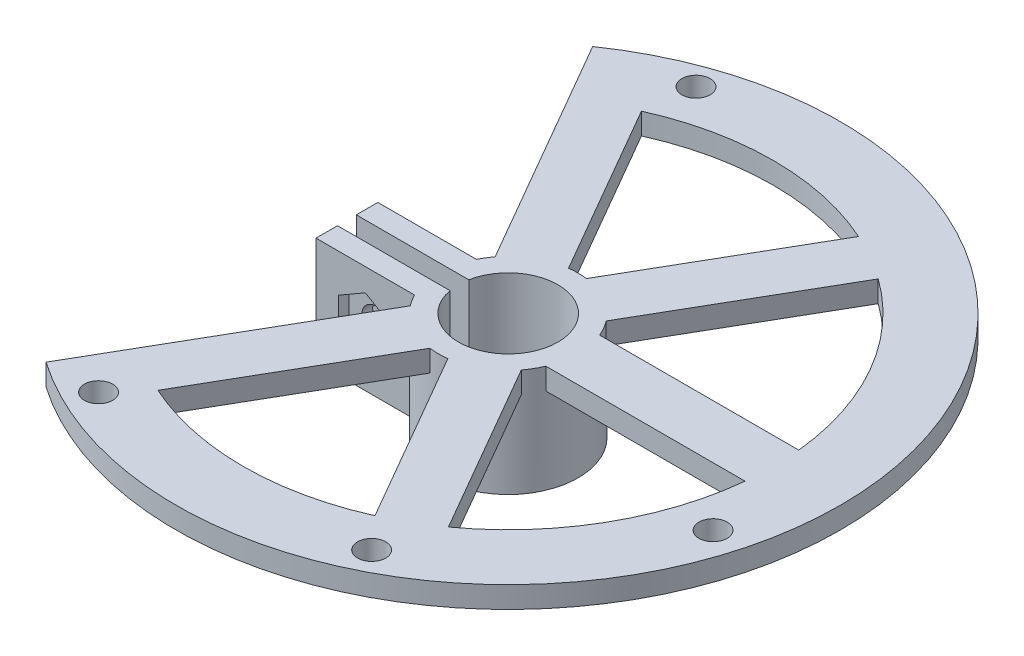
SolidWorks part; units mm, degrees
ref_plane "Front Plane" through (0, 0, 0) normal (0, 0, 1) x (1, 0, 0)
ref_plane "Top Plane" through (0, 0, 0) normal (0, 1, 0) x (1, 0, 0)
ref_plane "Right Plane" through (0, 0, 0) normal (1, 0, 0) x (0, 0, -1)
sketch "Sketch1" plane through (0, 0, 0) normal (0, 1, 0) x (1, 0, 0)
  line L0 (0, 0) -> (21.59, -6.35) construction
  line L1 (0, 0) -> (-7.62, 0) construction
  line L2 (0, 0) -> (0, 21.59) construction
  line L3 (0, 21.59) -> (-7.62, 21.59) construction
  line L4 (-7.62, 0) -> (-7.62, 21.59) construction
  line L5 (0, 0) -> (21.59, 0) construction
  line L6 (0, 0) -> (0, -6.35) construction
  line L7 (0, -6.35) -> (21.59, -6.35) construction
  line L8 (21.59, 0) -> (21.59, -6.35) construction
  line L9 (0, 0) -> (-10.16, 0) construction
  line L10 (0, 0) -> (0, -20.32) construction
  line L11 (0, -20.32) -> (-10.16, -20.32) construction
  line L12 (-10.16, 0) -> (-10.16, -20.32) construction
  line L13 (0, 0) -> (10.16, 0) construction
  line L14 (0, 0) -> (0, -20.32) construction
  line L15 (0, -20.32) -> (10.16, -20.32) construction
  line L16 (10.16, 0) -> (10.16, -20.32) construction
  line L17 (23.6985, -2.54) -> (28.16, -2.54)
  line L18 (-13.208, -20.701) -> (0, 0) construction
  line L19 (0, 0) -> (19.812, 0) construction
  line L20 (0, 0) -> (0, -10.668) construction
  line L21 (0, -10.668) -> (19.812, -10.668) construction
  line L22 (19.812, 0) -> (19.812, -10.668) construction
  line L23 (0, 0) -> (6.223, 0) construction
  line L24 (0, 0) -> (0, -21.844) construction
  line L25 (0, -21.844) -> (6.223, -21.844) construction
  line L26 (6.223, 0) -> (6.223, -21.844) construction
  line L27 (0, 0) -> (12.065, 0) construction
  line L28 (0, 0) -> (0, 19.431) construction
  line L29 (0, 19.431) -> (12.065, 19.431) construction
  line L30 (12.065, 0) -> (12.065, 19.431) construction
  line L31 (0, 0) -> (-13.208, 0) construction
  line L32 (0, 0) -> (0, -26.289) construction
  line L33 (0, -26.289) -> (-13.208, -26.289) construction
  line L34 (-13.208, 0) -> (-13.208, -26.289) construction
  line L35 (0, 0) -> (-7.62, 0) construction
  line L36 (0, 0) -> (0, -26.289) construction
  line L37 (0, -26.289) -> (-7.62, -26.289) construction
  line L38 (-7.62, 0) -> (-7.62, -26.289) construction
  line L39 (0, 0) -> (-13.208, 0) construction
  line L40 (0, 0) -> (0, -20.701) construction
  line L41 (0, -20.701) -> (-13.208, -20.701) construction
  line L42 (-13.208, 0) -> (-13.208, -20.701) construction
  line L44 (-8.62, -26.289) -> (-12.208, -26.289)
  line L45 (-13.208, -25.289) -> (-13.208, -20.9928)
  line L47 (-13.051, -20.455) -> (-11.5519, -18.1054)
  line L48 (-7.62, -25.289) -> (-7.62, -19.6963)
  line L49 (0, 0) -> (29.16, 0) construction
  line L50 (0, 0) -> (0, -6.35) construction
  line L51 (0, -6.35) -> (29.16, -6.35) construction
  line L52 (29.16, 0) -> (29.16, -6.35) construction
  line L53 (0, 0) -> (23.368, 0) construction
  line L54 (0, 0) -> (0, -2.54) construction
  line L55 (0, -2.54) -> (23.368, -2.54) construction
  line L56 (23.368, 0) -> (23.368, -2.54) construction
  line L57 (21.59, -8.35) -> (28.16, -8.35)
  line L58 (29.16, -7.35) -> (29.16, -3.54)
  line L59 (23.1026, -2.737) -> (20.3981, -4.7439)
  circle A0 centre (-7.62, 21.59) radius 1.05
  circle A1 centre (-10.16, -20.32) radius 1.05
  circle A2 centre (10.16, -20.32) radius 1.05
  circle A3 centre (21.59, -6.35) radius 1.05
  circle A4 centre (0, 0) radius 20 construction
  arc A5 (20.3981, -4.7439) -> (21.59, -8.35) centre (21.59, -6.35) ccw
  arc A10 (10.16, -20.32) -> (8.1222, -21.2169) centre (0, 0) cw construction
  arc A11 (8.8372, -23.0848) -> (11.0544, -22.1089) centre (0, 0) ccw
  arc A12 (7.4071, -19.3491) -> (9.2656, -18.5311) centre (0, 0) ccw
  arc A13 (7.4071, -19.3491) -> (8.8372, -23.0848) centre (8.1222, -21.2169) ccw
  arc A14 (11.0544, -22.1089) -> (9.2656, -18.5311) centre (10.16, -20.32) ccw
  arc A15 (-7.62, 21.59) -> (10.2434, 20.4759) centre (0, 0) cw construction
  arc A16 (11.183, 22.354) -> (-8.3189, 23.5703) centre (0, 0) ccw
  arc A17 (9.3039, 18.5979) -> (-6.9211, 19.6097) centre (0, 0) ccw
  arc A18 (9.3039, 18.5979) -> (11.183, 22.354) centre (10.2434, 20.4759) ccw
  arc A19 (-8.3189, 23.5703) -> (-6.9211, 19.6097) centre (-7.62, 21.59) ccw
  arc A21 (-10.2108, -17.7761) -> (-8.2191, -18.7802) centre (0, 0) ccw
  arc A22 (-7.62, -25.289) -> (-8.62, -26.289) centre (-8.62, -25.289) cw
  arc A23 (-12.208, -26.289) -> (-13.208, -25.289) centre (-12.208, -25.289) cw
  arc A24 (-13.208, -20.9928) -> (-13.051, -20.455) centre (-12.208, -20.9928) cw
  arc A25 (-8.2191, -18.7802) -> (-7.62, -19.6963) centre (-8.62, -19.6963) cw
  arc A26 (-11.5519, -18.1054) -> (-10.2108, -17.7761) centre (-10.7089, -18.6432) cw
  arc A27 (23.59, -6.35) -> (21.59, -4.35) centre (21.59, -6.35) ccw construction
  arc A28 (21.59, -8.35) -> (23.59, -6.35) centre (21.59, -6.35) ccw construction
  arc A29 (21.59, -4.35) -> (20.3981, -4.7439) centre (21.59, -6.35) ccw construction
  arc A30 (28.16, -8.35) -> (29.16, -7.35) centre (28.16, -7.35) ccw
  arc A31 (28.16, -2.54) -> (29.16, -3.54) centre (28.16, -3.54) cw
  arc A32 (23.6985, -2.54) -> (23.1026, -2.737) centre (23.6985, -3.54) ccw
  point P34 (9.1521, -20.7934)
  point P44 (1.4251, 22.8509)
  point P57 (-10.7576, -16.8604)
  point P59 (-7.62, -18.4915)
  point P73 (-7.62, -19.0312)
  point P76 (-11.0265, -17.282)
  point P84 (29.16, -2.54)
  dimension "D1" = 7.62
  dimension "D8" = 2.1
  dimension "D9" = 40
  dimension "D13" = 29.16
  dimension "D15" = 2
  dimension "D18" = 2.1
  dimension "D23" = 0.5
  dimension "D24" = 1
  dimension "D27" = 4
  dimension "D28" = 1
  dimension "D2" = 21.59
  dimension "D3" = 10.16
  dimension "D4" = 20.32
  dimension "D5" = 10.16
  dimension "D6" = 6.35
  dimension "D7" = 21.59
  dimension "D10" = 6.223
  dimension "D11" = 19.812
  dimension "D12" = 10.668
  dimension "D14" = 21.844
  dimension "D16" = 12.065
  dimension "D17" = 19.431
  dimension "D19" = 13.208
  dimension "D20" = 26.289
  dimension "D21" = 7.62
  dimension "D22" = 20.701
  dimension "D25" = 2.54
  dimension "D26" = 23.368
extrude "Boss-Extrude1" [suppressed] add sketch "Sketch1" along normal blind 2
sketch "Sketch2" plane through (0, 0, 0) normal (0, 1, 0) x (1, 0, 0)
  line L0 (-3.7, 0) -> (-12, 0) construction
  line L1 (-4.979, 1.5) -> (-12, 1.5) construction
  line L2 (-4.979, -1.5) -> (-12, -1.5) construction
  line L3 (-4.6637, 2.3) -> (-12, 2.3)
  line L4 (-3.6332, -0.7) -> (-12, -0.7)
  line L5 (-3.6332, 0.7) -> (-12, 0.7)
  line L6 (-4.6637, -2.3) -> (-12, -2.3)
  line L7 (-12, 2.3) -> (-12, 0.7)
  line L8 (-12, -0.7) -> (-12, -2.3)
  line L9 (0, 2.3) -> (-2.8983, 2.3) construction
  line L10 (0, 2.3) -> (-12, 2.3) construction
  line L11 (0, 1.5) -> (-3.3823, 1.5) construction
  line L12 (0, 1.5) -> (-12, 1.5) construction
  line L13 (0, 0.7) -> (-3.6332, 0.7) construction
  line L14 (0, 0.7) -> (-12, 0.7) construction
  line L15 (0, 0) -> (-3.7, 0) construction
  line L16 (0, 0) -> (-12, 0) construction
  line L17 (0, -0.7) -> (-3.6332, -0.7) construction
  line L18 (0, -0.7) -> (-12, -0.7) construction
  line L19 (0, -1.5) -> (-3.3823, -1.5) construction
  line L20 (0, -1.5) -> (-12, -1.5) construction
  line L21 (0, -2.3) -> (-2.8983, -2.3) construction
  line L22 (0, -2.3) -> (-12, -2.3) construction
  line L23 (-2.8983, 2.3) -> (-4.6637, 2.3) construction
  line L24 (-3.3823, 1.5) -> (-4.979, 1.5) construction
  line L25 (-2.8983, -2.3) -> (-4.6637, -2.3) construction
  line L26 (-3.3823, -1.5) -> (-4.979, -1.5) construction
  arc A0 (-3.6332, -0.7) -> (-3.6332, 0.7) centre (0, 0) ccw
  arc A1 (-4.6637, -2.3) -> (-4.6637, 2.3) centre (0, 0) ccw
  arc A2 (-4.979, -1.5) -> (-4.6637, -2.3) centre (0, 0) ccw construction
  arc A3 (-5.1527, -0.7) -> (-4.979, -1.5) centre (0, 0) ccw construction
  arc A4 (-4.6637, 2.3) -> (-4.979, 1.5) centre (0, 0) ccw construction
  arc A5 (-5.2, 0) -> (-5.1527, -0.7) centre (0, 0) ccw construction
  arc A6 (-4.979, 1.5) -> (-5.1527, 0.7) centre (0, 0) ccw construction
  arc A7 (-5.1527, 0.7) -> (-5.2, 0) centre (0, 0) ccw construction
  arc A8 (-3.6332, 0.7) -> (-3.7, 0) centre (0, 0) ccw construction
  arc A9 (-3.7, 0) -> (-3.6332, -0.7) centre (0, 0) ccw construction
  dimension "D1" = 7.4
  dimension "D2" = 1.5
  dimension "D3" = 12
  dimension "D4" = 1.5
  dimension "D5" = 1.5
  dimension "D6" = 0.8
  dimension "D7" = 0.8
extrude "Boss-Extrude2" add sketch "Sketch2" along normal blind 8 from offset 10 separate body
sketch "Sketch3" [suppressed] plane through (0, 2, 0) normal (0, 1, 0) x (1, 0, 0)
  line L0 (-7.62, -22.82) -> (-13.208, -22.82)
  line L1 (8.8372, -23.0848) -> (7.4071, -19.3491)
  line L2 (-7.62, -22.82) -> (-7.62, -19.6963) construction
  line L3 (-13.208, -20.9928) -> (-13.208, -22.82) construction
  line L4 (-7.62, -25.289) -> (-7.62, -19.6963)
  line L5 (-11.5519, -18.1054) -> (-13.051, -20.455)
  line L6 (-13.208, -20.9928) -> (-13.208, -25.289)
  line L7 (-12.208, -26.289) -> (-8.62, -26.289)
  line L8 (-7.62, -25.289) -> (-7.62, -22.82) construction
  line L9 (-11.5519, -18.1054) -> (-13.051, -20.455) construction
  line L10 (-13.208, -22.82) -> (-13.208, -25.289)
  line L11 (-12.208, -26.289) -> (-8.62, -26.289)
  line L13 (23.6985, -2.54) -> (23.6985, -8.35)
  line L14 (21.59, -8.35) -> (23.6985, -8.35) construction
  line L15 (-1.2669, 22.8602) -> (0, 0) construction
  line L16 (0, 0) -> (10.3329, 20.4309) construction
  line L17 (29.16, -7.35) -> (29.16, -3.54)
  line L18 (28.16, -2.54) -> (23.6985, -2.54)
  line L19 (23.1026, -2.737) -> (20.3981, -4.7439)
  line L20 (21.59, -8.35) -> (28.16, -8.35)
  line L21 (29.16, -7.35) -> (29.16, -3.54)
  line L22 (28.16, -2.54) -> (23.6985, -2.54)
  line L23 (23.1026, -2.737) -> (20.3981, -4.7439) construction
  line L24 (23.6985, -8.35) -> (28.16, -8.35)
  arc A1 (10.3329, 20.4309) -> (-1.2669, 22.8602) centre (0, 0) ccw construction
  arc A2 (11.2355, 22.2157) -> (-1.3776, 24.8571) centre (0, 0) ccw
  arc A3 (9.4303, 18.6462) -> (-1.1562, 20.8632) centre (0, 0) ccw
  arc A4 (7.4071, -19.3491) -> (8.8372, -23.0848) centre (8.1222, -21.2169) ccw
  arc A5 (8.8372, -23.0848) -> (11.0544, -22.1089) centre (0, 0) ccw
  arc A6 (-8.62, -26.289) -> (-7.62, -25.289) centre (-8.62, -25.289) ccw
  arc A7 (-7.62, -19.6963) -> (-8.2191, -18.7802) centre (-8.62, -19.6963) ccw
  arc A8 (-10.2108, -17.7761) -> (-8.2191, -18.7802) centre (0, 0) ccw
  arc A9 (-10.2108, -17.7761) -> (-11.5519, -18.1054) centre (-10.7089, -18.6432) ccw
  arc A10 (-13.051, -20.455) -> (-13.208, -20.9928) centre (-12.208, -20.9928) ccw
  arc A11 (-13.208, -25.289) -> (-12.208, -26.289) centre (-12.208, -25.289) ccw
  arc A12 (-8.62, -26.289) -> (-7.62, -25.289) centre (-8.62, -25.289) ccw construction
  arc A13 (-7.62, -19.6963) -> (-8.2191, -18.7802) centre (-8.62, -19.6963) ccw construction
  arc A14 (-10.2108, -17.7761) -> (-8.2191, -18.7802) centre (0, 0) ccw construction
  arc A15 (-10.2108, -17.7761) -> (-11.5519, -18.1054) centre (-10.7089, -18.6432) ccw construction
  arc A16 (-13.051, -20.455) -> (-13.208, -20.9928) centre (-12.208, -20.9928) ccw construction
  arc A17 (-13.208, -25.289) -> (-12.208, -26.289) centre (-12.208, -25.289) ccw
  arc A18 (11.0544, -22.1089) -> (9.2656, -18.5311) centre (10.16, -20.32) ccw
  arc A19 (7.4071, -19.3491) -> (9.2656, -18.5311) centre (0, 0) ccw
  arc A20 (7.4071, -19.3491) -> (8.8372, -23.0848) centre (8.1222, -21.2169) ccw construction
  arc A21 (8.8372, -23.0848) -> (11.0544, -22.1089) centre (0, 0) ccw construction
  arc A22 (11.0544, -22.1089) -> (9.2656, -18.5311) centre (10.16, -20.32) ccw construction
  arc A23 (7.4071, -19.3491) -> (9.2656, -18.5311) centre (0, 0) ccw construction
  arc A25 (9.4303, 18.6462) -> (11.2355, 22.2157) centre (10.3329, 20.4309) ccw
  arc A26 (28.16, -8.35) -> (29.16, -7.35) centre (28.16, -7.35) ccw
  arc A27 (29.16, -3.54) -> (28.16, -2.54) centre (28.16, -3.54) ccw
  arc A32 (23.6985, -2.54) -> (23.1026, -2.737) centre (23.6985, -3.54) ccw
  arc A33 (20.3981, -4.7439) -> (21.59, -8.35) centre (21.59, -6.35) ccw
  arc A34 (28.16, -8.35) -> (29.16, -7.35) centre (28.16, -7.35) ccw
  arc A35 (29.16, -3.54) -> (28.16, -2.54) centre (28.16, -3.54) ccw
  arc A36 (23.6985, -2.54) -> (23.1026, -2.737) centre (23.6985, -3.54) ccw construction
  arc A37 (20.3981, -4.7439) -> (21.59, -8.35) centre (21.59, -6.35) ccw construction
  arc A38 (-1.3776, 24.8571) -> (-1.1562, 20.8632) centre (-1.2669, 22.8602) ccw
  arc A39 (9.4303, 18.6462) -> (11.2355, 22.2157) centre (10.3329, 20.4309) ccw construction
  spline S0 degree 3 poles (7.4071, -19.3491) (4.2211, -20.5688) (0.8751, -21.8378) (-5.0583, -22.82) (-7.62, -22.82) knots 0 0 0 0 0.561797 1 1 1 1
  spline S1 degree 3 poles (8.8372, -23.0848) (5.6188, -24.3168) (0.8822, -25.8001) (-5.6018, -26.289) (-8.62, -26.289) knots 0 0 0 0 0.494946 1 1 1 1
  point P0 (-7.62, -22.82)
  point P21 (-10.16, -20.32)
  point P38 (4.6929, 22.4091)
  dimension "D5" = 30
  dimension "D3" = 2.5
  dimension "D4" = 0
  dimension "D1" = 0
  dimension "D2" = 0
extrude "Boss-Extrude3" [suppressed] add sketch "Sketch3" along normal blind 2
sketch "Sketch5" [suppressed] plane through (0, 4, 0) normal (0, 1, 0) x (1, 0, 0)
  line L0 (23.6985, -8.35) -> (28.16, -8.35) construction
  line L1 (29.16, -7.35) -> (29.16, -3.54) construction
  line L2 (28.16, -2.54) -> (23.6985, -2.54) construction
  line L3 (23.6985, -2.54) -> (23.6985, -8.35) construction
  line L4 (8.8372, -23.0848) -> (7.4071, -19.3491) construction
  line L5 (-7.62, -22.82) -> (-13.208, -22.82) construction
  line L6 (-13.208, -22.82) -> (-13.208, -25.289) construction
  line L7 (-12.208, -26.289) -> (-8.62, -26.289) construction
  line L8 (23.6985, -8.35) -> (28.16, -8.35) construction
  line L9 (29.16, -7.35) -> (29.16, -3.54)
  line L10 (28.16, -2.54) -> (23.6985, -2.54) construction
  line L11 (23.6985, -2.54) -> (23.6985, -8.35)
  line L12 (8.8372, -23.0848) -> (7.4071, -19.3491)
  line L13 (-7.62, -22.82) -> (-13.208, -22.82)
  line L14 (-13.208, -22.82) -> (-13.208, -25.289)
  line L15 (-12.208, -26.289) -> (-8.62, -26.289)
  line L16 (2.9834, -20.9706) -> (4.0553, -24.7219) construction
  arc A0 (9.4303, 18.6462) -> (11.2355, 22.2157) centre (10.3329, 20.4309) ccw construction
  arc A1 (11.2355, 22.2157) -> (-1.3776, 24.8571) centre (0, 0) ccw construction
  arc A2 (-1.3776, 24.8571) -> (-1.1562, 20.8632) centre (-1.2669, 22.8602) ccw construction
  arc A3 (9.4303, 18.6462) -> (-1.1562, 20.8632) centre (0, 0) ccw construction
  arc A4 (28.16, -8.35) -> (29.16, -7.35) centre (28.16, -7.35) ccw construction
  arc A5 (29.16, -3.54) -> (28.16, -2.54) centre (28.16, -3.54) ccw construction
  arc A6 (-13.208, -25.289) -> (-12.208, -26.289) centre (-12.208, -25.289) ccw construction
  arc A7 (9.4303, 18.6462) -> (11.2355, 22.2157) centre (10.3329, 20.4309) ccw construction
  arc A8 (11.2355, 22.2157) -> (-1.3776, 24.8571) centre (0, 0) ccw
  arc A9 (-1.3776, 24.8571) -> (-1.1562, 20.8632) centre (-1.2669, 22.8602) ccw
  arc A10 (9.4303, 18.6462) -> (-1.1562, 20.8632) centre (0, 0) ccw
  arc A11 (28.16, -8.35) -> (29.16, -7.35) centre (28.16, -7.35) ccw construction
  arc A12 (29.16, -3.54) -> (29.1551, -3.4413) centre (28.16, -3.54) ccw
  arc A13 (-13.208, -25.289) -> (-12.208, -26.289) centre (-12.208, -25.289) ccw
  arc A14 (29.1551, -3.4413) -> (28.16, -2.54) centre (28.16, -3.54) ccw construction
  spline S0 degree 3 poles (2986.1043, 138.0269) (-226.9594, 31.6479) (87.9124, -84.0037) (-1.1957, 30.2505) (2916.2447, 714.3091) knots -8.140583 -8.140583 -8.140583 -8.140583 0.505054 7.064814 7.064814 7.064814 7.064814 only from (-8.62, -26.289) to (8.8372, -23.0848) construction
  spline S1 degree 3 poles (1953.9415, 439.1191) (-28.0065, -0.4252) (91.668, -33.8744) (-180.4518, -23.8863) (1461.6685, 1330.9522) knots -5.051989 -5.051989 -5.051989 -5.051989 0.561797 7.253557 7.253557 7.253557 7.253557 only from (7.4071, -19.3491) to (-7.62, -22.82) construction
  spline S2 degree 3 poles (-8.62, -26.289) (-5.6018, -26.289) (-0.9023, -25.9346) (2.8793, -25.0579) (4.0553, -24.7219) knots 0 0 0 0 0.505054 0.724787 0.724787 0.724787 0.724787
  spline S3 degree 3 poles (7.4071, -19.3491) (4.2211, -20.5688) (0.8751, -21.8378) (-5.0583, -22.82) (-7.62, -22.82) knots 0 0 0 0 0.561797 1 1 1 1
  spline S4 degree 3 poles (23.6985, -8.35) (23.6985, -10.1666) (23.9904, -13.2388) (16.619, -21.2319) (11.7258, -21.979) (8.8372, -23.0848) knots 0 0 0 0 0.420129 0.520129 1 1 1 1
  spline S5 degree 2 poles (9.4303, 18.6462) (21.7255, 11.4557) (23.6985, -2.54) knots 0 0 0 1 1 1
  spline S6 degree 2 poles (11.2355, 22.2157) (28.2782, 14.7461) (29.16, -3.54) knots 0 0 0 1 1 1
  spline S7 degree 3 poles (29.16, -7.35) (29.16, -13.3885) (27.9427, -21.7873) (5.7926, -30.8014) (4.0553, -24.7219) knots 0 0 0 0 0.521358 1 1 1 1
  spline S8 degree 3 poles (4.0553, -24.7219) (5.5283, -24.301) (7.0476, -23.7698) (8.8372, -23.0848) knots 0.724787 0.724787 0.724787 0.724787 1 1 1 1 construction
  point P4 (5.6812, -24.2202)
  point P10 (5.1029, -26.5245)
  point P17 (16.0456, -26.9706)
  point P24 (22.1682, -22.5397)
  point P25 (15.8264, -26.289)
  point P30 (21.4636, -22.82)
  point P32 (14.9974, -26.5603)
  point P34 (4.5649, -24.5724)
  point P37 (15.7136, -25.6084)
  point P39 (22.2008, -22.3133)
  spline M19 degree 3 poles (-8.62, -26.289) (-5.6018, -26.289) (0.8822, -25.8001) (5.6188, -24.3168) (8.8372, -23.0848) knots 0 0 0 0 0.505054 1 1 1 1
  line M20 (8.8372, -23.0848) -> (7.4071, -19.3491)
  spline M21 degree 3 poles (7.4071, -19.3491) (4.2211, -20.5688) (0.8751, -21.8378) (-5.0583, -22.82) (-7.62, -22.82) knots 0 0 0 0 0.561797 1 1 1 1
  line M22 (-7.62, -22.82) -> (-13.208, -22.82)
  line M23 (-13.208, -22.82) -> (-13.208, -25.289)
  arc M24 (-13.208, -25.289) -> (-12.208, -26.289) centre (-12.208, -25.289) ccw
  line M25 (-12.208, -26.289) -> (-8.62, -26.289)
  dimension "D1" = 5
extrude "Boss-Extrude5" [suppressed] add sketch "Sketch5" along normal blind 2 from surface contours M25 M19 M20 M21 M22 M23 M24 | S7 L9 S6 A8 A9 A10 S5 L11 S4 M19 starting at face at (-5.9246, 18, 0)
sketch "Sketch6" plane through (0, 0, 2.3) normal (0, 0, 1) x (1, 0, 0)
  line L0 (-12, 18) -> (-4.6637, 10) construction
  line L1 (-4.6637, 18) -> (-12, 10) construction
  circle A0 centre (-8.3318, 14) radius 1.05
  point P11 (-8.3318, 14)
  dimension "D1" = 2.1
extrude "Cut-Extrude1" cut sketch "Sketch6" against normal through all both and the other way through all
sketch "Sketch7" plane through (0, 0, 2.3) normal (0, 0, 1) x (1, 0, 0)
  line L1 (-6.3318, 15.1547) -> (-8.3318, 16.3094)
  line L2 (-8.3318, 16.3094) -> (-10.3318, 15.1547)
  line L3 (-10.3318, 15.1547) -> (-10.3318, 12.8453)
  line L4 (-10.3318, 12.8453) -> (-8.3318, 11.6906)
  line L5 (-8.3318, 11.6906) -> (-6.3318, 12.8453)
  line L6 (-6.3318, 12.8453) -> (-6.3318, 15.1547)
  circle A0 centre (-8.3318, 14) radius 2 construction
  dimension "D1" = 4
extrude "Cut-Extrude2" cut sketch "Sketch7" against normal blind 0.8
sketch "Sketch8" plane through (0, 18, 0) normal (0, -1, 0) x (1, 0, 0)
  line L0 (-9.8592, 17.0767) -> (0, 0) construction
  line L1 (-24.7185, 0) -> (-12.3592, -21.4068) construction
  line L2 (-12.3592, -21.4068) -> (12.3592, -21.4068) construction
  line L3 (12.3592, -21.4068) -> (24.7185, 0) construction
  line L4 (24.7185, 0) -> (12.3592, 21.4068) construction
  line L5 (12.3592, 21.4068) -> (-12.3592, 21.4068) construction
  line L6 (-12.3592, 21.4068) -> (-24.7185, 0) construction
  line L7 (0, 0) -> (9.8592, -17.0767) construction
  line L8 (-9.8592, -17.0767) -> (0, 0) construction
  line L9 (0, 0) -> (9.8592, 17.0767) construction
  line L10 (0, 0) -> (19.7185, 0) construction
  line L11 (-10.5867, -22.3366) -> (-10.0498, -21.4068) construction
  line L12 (0.6679, -5.1569) -> (8.0763, -17.9886)
  line L13 (1.1547, -2) -> (3.4641, -2) construction
  line L14 (1.7321, -1) -> (3.4641, 2) construction
  line L15 (-14.0913, 20.4068) -> (-14.0508, 20.3366) construction
  line L16 (-14.0508, -20.3366) -> (-13.5139, -19.4068) construction
  line L17 (2.3094, 0) -> (3.4641, -2) construction
  line L18 (4.8, 2) -> (19.6168, 2)
  line L19 (0.6679, 5.1569) -> (8.0763, 17.9886)
  line L20 (-10.6272, 22.4068) -> (-10.5867, 22.3366) construction
  line L21 (-13.5139, -19.4068) -> (-11.5404, -15.9886) construction
  line L22 (-11.5404, -15.9886) -> (-4.1321, -3.1569)
  line L23 (-14.0913, -20.4068) -> (-1.7321, 1) construction
  line L24 (-12.3592, -21.4068) -> (-9.8592, -17.0767) construction
  line L25 (-12.3592, -21.4068) -> (0, 0) construction
  line L26 (-10.0498, -21.4068) -> (-8.0763, -17.9886) construction
  line L27 (-8.0763, -17.9886) -> (-0.6679, -5.1569)
  line L28 (-10.6272, -22.4068) -> (1.7321, -1) construction
  line L29 (11.5404, -15.9886) -> (13.5139, -19.4068) construction
  line L30 (13.5139, -19.4068) -> (14.0508, -20.3366) construction
  line L31 (1.7321, 1) -> (14.0913, -20.4068) construction
  line L32 (9.8592, -17.0767) -> (12.3592, -21.4068) construction
  line L33 (0, 0) -> (12.3592, -21.4068) construction
  line L34 (8.0763, -17.9886) -> (10.0498, -21.4068) construction
  line L35 (10.0498, -21.4068) -> (10.5867, -22.3366) construction
  line L36 (-1.7321, -1) -> (10.6272, -22.4068) construction
  line L37 (19.6168, 2) -> (23.5638, 2) construction
  line L38 (24.6374, 2) -> (24.7185, 2) construction
  line L39 (0, 2) -> (24.7185, 2) construction
  line L40 (19.7185, 0) -> (24.7185, 0) construction
  line L41 (0, 0) -> (24.7185, 0) construction
  line L42 (19.6168, -2) -> (23.5638, -2) construction
  line L43 (24.6374, -2) -> (24.7185, -2) construction
  line L44 (0, -2) -> (24.7185, -2) construction
  line L45 (8.0763, 17.9886) -> (10.0498, 21.4068) construction
  line L46 (10.5867, 22.3366) -> (10.6272, 22.4068) construction
  line L47 (-1.7321, 1) -> (10.6272, 22.4068) construction
  line L48 (9.8592, 17.0767) -> (12.3592, 21.4068) construction
  line L49 (0, 0) -> (12.3592, 21.4068) construction
  line L50 (11.5404, 15.9886) -> (13.5139, 19.4068) construction
  line L51 (14.0508, 20.3366) -> (14.0913, 20.4068) construction
  line L52 (1.7321, -1) -> (14.0913, 20.4068) construction
  line L53 (-13.5139, 19.4068) -> (-11.5404, 15.9886) construction
  line L54 (-11.5404, 15.9886) -> (-4.1321, 3.1569)
  line L55 (-14.0913, 20.4068) -> (-1.7321, -1) construction
  line L56 (-12.3592, 21.4068) -> (-9.8592, 17.0767) construction
  line L57 (-12.3592, 21.4068) -> (0, 0) construction
  line L58 (-10.0498, 21.4068) -> (-8.0763, 17.9886) construction
  line L59 (-8.0763, 17.9886) -> (-0.6679, 5.1569)
  line L60 (-10.6272, 22.4068) -> (1.7321, 1) construction
  line L61 (13.5139, 19.4068) -> (14.0508, 20.3366) construction
  line L62 (10.0498, 21.4068) -> (10.5867, 22.3366) construction
  line L63 (23.5638, -2) -> (24.6374, -2) construction
  line L64 (23.5638, 2) -> (24.6374, 2) construction
  line L65 (10.5867, -22.3366) -> (10.6272, -22.4068) construction
  line L66 (14.0508, -20.3366) -> (14.0913, -20.4068) construction
  line L67 (-14.0913, -20.4068) -> (-14.0508, -20.3366) construction
  line L68 (-10.6272, -22.4068) -> (-10.5867, -22.3366) construction
  line L69 (-14.0508, 20.3366) -> (-13.5139, 19.4068) construction
  line L70 (-10.5867, 22.3366) -> (-10.0498, 21.4068) construction
  line L71 (-4.6637, -2.3) -> (-12, -2.3) construction
  line L72 (-1.1547, -2) -> (0, -4) construction
  line L73 (-4.1321, 3.1569) -> (-2.3094, 0) construction
  line L74 (-2.3094, 0) -> (-1.7321, -1) construction
  line L75 (-2.3094, 0) -> (-1.7321, 1) construction
  line L76 (-1.7321, -1) -> (-1.1547, -2) construction
  line L77 (-4.1321, -3.1569) -> (-2.3094, 0) construction
  line L78 (-1.7321, 1) -> (-1.1547, 2) construction
  line L79 (-1.1547, 2) -> (0, 4) construction
  line L80 (0, 4) -> (1.1547, 2) construction
  line L81 (1.1547, 2) -> (1.7321, 1) construction
  line L82 (0, 2) -> (1.1547, 2) construction
  line L83 (1.1547, 2) -> (3.4641, 2) construction
  line L84 (1.7321, 1) -> (2.3094, 0) construction
  line L85 (0, -4) -> (1.1547, -2) construction
  line L86 (1.1547, -2) -> (1.7321, -1) construction
  line L87 (0, -2) -> (1.1547, -2) construction
  line L88 (-0.6679, 5.1569) -> (0, 4) construction
  line L89 (0, 4) -> (0.6679, 5.1569) construction
  line L90 (3.4641, 2) -> (4.1321, 3.1569) construction
  line L91 (4.1321, 3.1569) -> (11.5404, 15.9886)
  line L92 (3.4641, 2) -> (4.8, 2) construction
  line L93 (3.4641, -2) -> (4.8, -2) construction
  line L94 (4.8, -2) -> (19.6168, -2)
  line L95 (3.4641, -2) -> (4.1321, -3.1569) construction
  line L96 (4.1321, -3.1569) -> (11.5404, -15.9886)
  line L97 (-0.6679, -5.1569) -> (0, -4) construction
  line L98 (0, -4) -> (0.6679, -5.1569) construction
  line L99 (-14.0508, 20.3366) -> (-11.5404, 15.9886)
  line L100 (-14.0508, -20.3366) -> (-11.5404, -15.9886)
  circle A0 centre (0, 0) radius 24.7185 construction
  arc A1 (-4.1321, 3.1569) -> (-0.6679, 5.1569) centre (0, 0) cw
  arc A2 (11.0544, 22.1089) -> (8.8372, 23.0848) centre (0, 0) ccw construction
  circle A3 centre (0, 0) radius 24.7185 construction
  arc A4 (11.5404, -15.9886) -> (19.6168, -2) centre (0, 0) ccw
  arc A5 (8.0763, -17.9886) -> (9.8592, -17.0767) centre (0, 0) ccw construction
  circle A6 centre (0, 0) radius 19.7185 construction
  arc A7 (9.8592, -17.0767) -> (11.5404, -15.9886) centre (0, 0) ccw construction
  arc A8 (19.7185, 0) -> (19.6168, 2) centre (0, 0) ccw construction
  arc A9 (19.6168, 2) -> (11.5404, 15.9886) centre (0, 0) ccw
  arc A10 (19.6168, -2) -> (19.7185, 0) centre (0, 0) ccw construction
  arc A11 (9.8592, 17.0767) -> (8.0763, 17.9886) centre (0, 0) ccw construction
  arc A12 (8.0763, 17.9886) -> (-8.0763, 17.9886) centre (0, 0) ccw
  arc A13 (11.5404, 15.9886) -> (9.8592, 17.0767) centre (0, 0) ccw construction
  arc A14 (-11.5404, -15.9886) -> (-9.8592, -17.0767) centre (0, 0) ccw construction
  arc A15 (-8.0763, -17.9886) -> (8.0763, -17.9886) centre (0, 0) ccw
  arc A16 (-9.8592, -17.0767) -> (-8.0763, -17.9886) centre (0, 0) ccw construction
  arc A17 (-9.8592, 17.0767) -> (-11.5404, 15.9886) centre (0, 0) ccw construction
  arc A18 (-11.5404, 15.9886) -> (-11.5404, -15.9886) centre (0, 0) ccw construction
  arc A19 (-8.0763, 17.9886) -> (-9.8592, 17.0767) centre (0, 0) ccw construction
  arc A20 (-4.6637, -2.3) -> (-4.6637, 2.3) centre (0, 0) ccw construction
  arc A21 (-4.6637, 2.3) -> (-4.1321, 3.1569) centre (0, 0) cw construction
  arc A22 (-4.1321, -3.1569) -> (-4.6637, -2.3) centre (0, 0) cw construction
  arc A23 (-0.6679, 5.1569) -> (0.6679, 5.1569) centre (0, 0) cw construction
  arc A24 (0.6679, 5.1569) -> (4.1321, 3.1569) centre (0, 0) cw
  arc A25 (4.1321, 3.1569) -> (4.8, 2) centre (0, 0) cw construction
  arc A26 (4.8, 2) -> (4.8, -2) centre (0, 0) cw
  arc A27 (4.8, -2) -> (4.1321, -3.1569) centre (0, 0) cw construction
  arc A28 (4.1321, -3.1569) -> (0.6679, -5.1569) centre (0, 0) cw
  arc A29 (0.6679, -5.1569) -> (-0.6679, -5.1569) centre (0, 0) cw construction
  arc A30 (-0.6679, -5.1569) -> (-4.1321, -3.1569) centre (0, 0) cw
  arc A31 (-14.0508, 20.3366) -> (-14.0508, -20.3366) centre (0, 0) cw
  dimension "D1" = 5
  dimension "D2" = 2
  dimension "D3" = 2
extrude "Boss-Extrude6" add sketch "Sketch8" along normal blind 1.6
sketch "Sketch9" plane through (0, 18, 0) normal (0, 1, 0) x (1, 0, 0)
  circle A0 centre (-7.62, 21.59) radius 1.05 construction
  circle A1 centre (-7.62, 21.59) radius 1.05
  circle A2 centre (-10.16, -20.32) radius 1.05 construction
  circle A3 centre (10.16, -20.32) radius 1.05 construction
  circle A4 centre (21.59, -6.35) radius 1.05 construction
  circle A5 centre (-10.16, -20.32) radius 1.05
  circle A6 centre (10.16, -20.32) radius 1.05
  circle A7 centre (21.59, -6.35) radius 1.05
extrude "Cut-Extrude3" cut sketch "Sketch9" against normal through all
